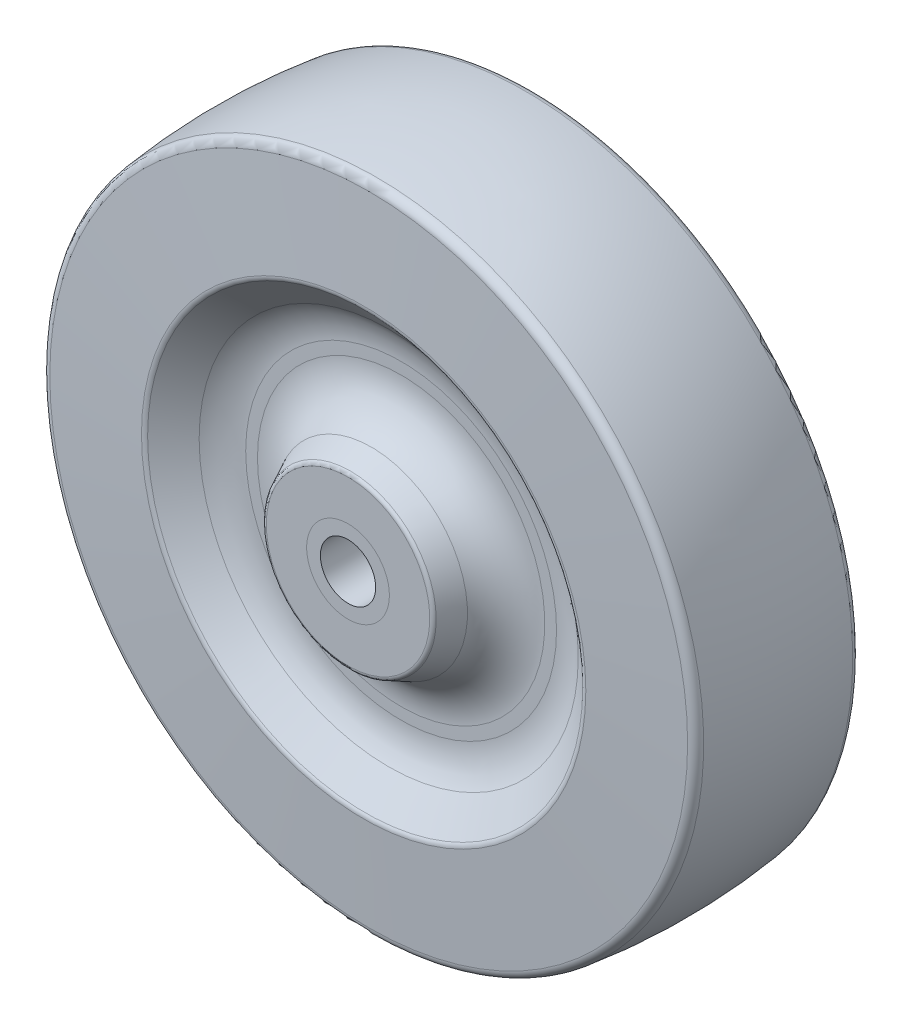
SolidWorks part; units mm, degrees
material "Rubber"
ref_plane "Front Plane" through (0, 0, 0) normal (0, 0, 1) x (1, 0, 0)
ref_plane "Top Plane" through (0, 0, 0) normal (0, 1, 0) x (1, 0, 0)
ref_plane "Right Plane" through (0, 0, 0) normal (1, 0, 0) x (0, 0, -1)
sketch "Sketch1" plane through (0, 0, 0) normal (1, 0, 0) x (0, 0, -1)
  line L0 (0, -38.1) -> (0, 38.1) construction
  line L1 (-11.8237, 0) -> (11.8237, 0) construction
  line L2 (-10.0457, 38.1) -> (10.0457, 38.1) construction
  point P0 (0, 3.175)
  point P3 (0, -3.175)
  point P4 (0, 0)
  point P8 (0, 0)
  point P11 (0, 38.1)
  point P14 (0, 4.7498)
  point P16 (0, -4.7498)
  point P17 (11.8237, 0)
  dimension "Wheel Diameter" = 76.2
  dimension "Hub Length" = 23.6474
  dimension "Wheel Width" = 20.0914
  dimension "For Axle Diameter" = 6.35
  dimension "D2" = 3.175
  dimension "Sleeve Bearing Diameter" = 9.4996
sketch "Sketch2" plane through (0, 0, 0) normal (1, 0, 0) x (0, 0, -1)
  line L6 (10.0457, 38.1) -> (0, 38.1) construction
  line L8 (0, 0) -> (0, 38.1) construction
  line L9 (0, -38.1) -> (0, 38.1) construction
  line L13 (5.7277, 20.066) -> (10.0457, 20.066) construction
  line L25 (5.7277, 12.7) -> (10.0457, 12.7) construction
  line L26 (-10.0457, 38.1) -> (0, 38.1) construction
  line L27 (10.0457, 25.212) -> (10.0457, 37.3738) construction
  line L28 (10.0457, 25.212) -> (5.7277, 20.066)
  line L29 (5.7277, 20.066) -> (5.7277, 12.7)
  line L30 (-11.8237, 0) -> (11.8237, 0) construction
  line L31 (11.8237, 9.7028) -> (5.7277, 12.7)
  line L33 (11.8237, 9.7028) -> (11.8237, 0)
  line L38 (-11.8237, 0) -> (11.8237, 0)
  line L39 (10.0457, 25.212) -> (9.4036, 37.4641)
  line L40 (-11.8237, 9.7028) -> (-11.8237, 0)
  line L41 (-11.8237, 9.7028) -> (-5.7277, 12.7)
  line L42 (-5.7277, 20.066) -> (-5.7277, 12.7)
  line L43 (-10.0457, 25.212) -> (-5.7277, 20.066)
  line L44 (-10.0457, 25.212) -> (-9.4036, 37.4641)
  arc A0 (0, 38.1) -> (10.0457, 37.3738) centre (0, -31.75) cw construction
  arc A1 (-9.4036, 37.4641) -> (9.4036, 37.4641) centre (0, -31.75) cw
  point P25 (0, 0)
  dimension "D3" = 12.7
  dimension "D4" = 9.7028
  dimension "D5" = 20.066
  dimension "D6" = 69.85
  dimension "D7" = 3
  dimension "D1" = 50
  dimension "D2" = 4.318
revolve "Revolve1" add sketch "Sketch2" angle 360 about L38
sketch "Sketch3" plane through (0, 0, 0) normal (1, 0, 0) x (0, 0, -1)
  line L12 (-11.8237, 0) -> (11.8237, 0) construction
  line L20 (11.8237, 0) -> (11.8237, 4.7498)
  line L21 (11.8237, 4.7498) -> (-11.8237, 4.7498)
  line L22 (-11.8237, 0) -> (-11.8237, 4.7498)
  line L25 (-11.8237, 0) -> (11.8237, 0)
  point P0 (0, 0)
revolve "Revolve2" add sketch "Sketch3" angle 360 about L25
sketch "Sketch6" plane through (0, 0, 0) normal (1, 0, 0) x (0, 0, -1)
  line L0 (0, -38.1) -> (0, 38.1) construction
  line L1 (-11.8237, 4.7498) -> (11.8237, 4.7498)
  line L5 (11.8237, 0) -> (-11.8237, 0)
  line L8 (-11.8237, 4.7498) -> (-11.8237, 0)
  line L9 (11.8237, 4.7498) -> (11.8237, 0)
  point P6 (0, 4.7498)
  point P11 (0, 0)
revolve "Cut-Revolve1" cut sketch "Sketch6" angle 360 about L1
sketch "Sketch4" plane through (0, 0, 0) normal (0, 0, 1) x (1, 0, 0)
  line L0 (0, -38.1) -> (0, 38.1) construction
  circle A0 centre (0, 0) radius 3.175
extrude "Cut-Extrude1" cut sketch "Sketch4" against normal through all both and the other way through all
fillet "Fillet1" radius 1.016 2 edges at (37.4641, 0, 9.4036) (37.4641, 0, -9.4036)
fillet "Fillet2" radius 6.096 4 edges at (20.066, 0, -5.7277) (12.7, 0, -5.7277) (12.7, 0, 5.7277) (20.066, 0, 5.7277)
fillet "Fillet3" radius 0.762 2 edges at (25.212, 0, 10.0457) (25.212, 0, -10.0457)
fillet "Fillet4" radius 0.508 2 edges at (9.7028, 0, -11.8237) (9.7028, 0, 11.8237)
sketch "Sketch8" plane through (0, 0, 0) normal (1, 0, 0) x (0, 0, -1)
  line L0 (0, -38.1) -> (0, 38.1) construction
  line L2 (-10.0457, 38.1) -> (10.0457, 38.1) construction
  line L3 (-11.8237, 0) -> (11.8237, 0) construction
  point P0 (10.0457, 33.02)
  point P5 (0, 0)
  point P6 (-10.0457, 33.02)
  point P12 (11.8237, -8.89)
  point P13 (-11.8237, -8.89)
  dimension "D1" = 5.08
  dimension "D2" = 8.89
sketch "Sketch9" plane through (0, 0, 0) normal (0, 0, 1) x (1, 0, 0)
  circle A0 centre (0, 0) radius 38.1 construction
  circle A1 centre (0, 0) radius 3.175 construction
ref_axis "Axis1" through (0, 0, -11.8237) along (0, 0, 1)
ref_point "Point1"
equation "\"D2@Sketch1\" = \"For Axle Diameter@Sketch1\" / 2"
